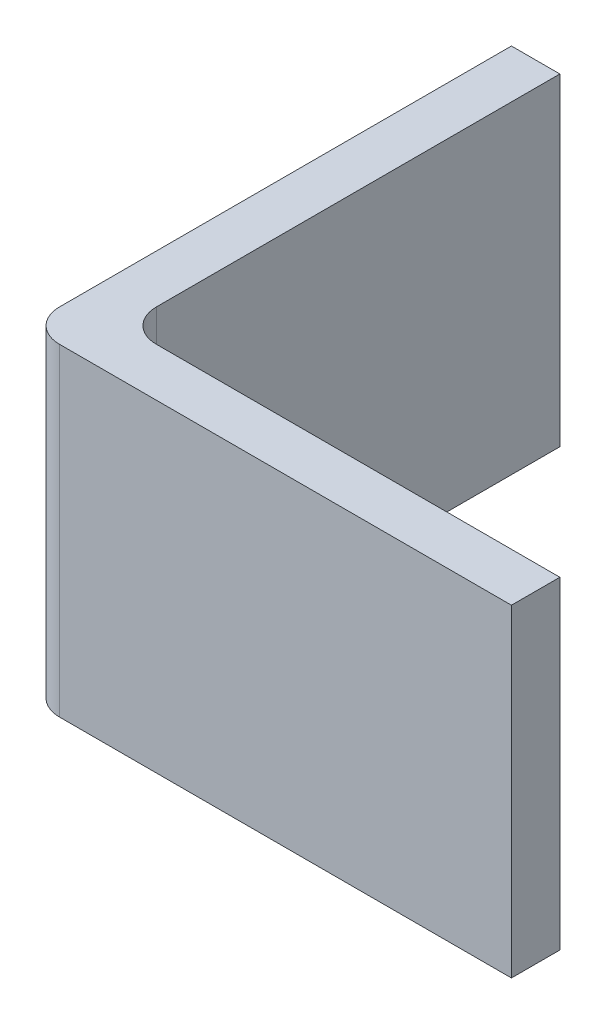
SolidWorks part; units mm, degrees
ref_plane "Спереди" through (0, 0, 0) normal (0, 0, 1) x (1, 0, 0)
ref_plane "Сверху" through (0, 0, 0) normal (0, 1, 0) x (1, 0, 0)
ref_plane "Справа" through (0, 0, 0) normal (1, 0, 0) x (0, 0, -1)
sketch "Эскиз1" plane through (0, 0, 0) normal (0, 1, 0) x (1, 0, 0)
  line L0 (0, 1) -> (0, 15)
  line L5 (0, 15) -> (1.5, 15)
  line L6 (1, 0) -> (15, 0)
  line L7 (15, 0) -> (15, 1.5)
  line L8 (15, 1.5) -> (2.5, 1.5)
  line L9 (1.5, 2.5) -> (1.5, 15)
  arc A0 (1, 0) -> (0, 1) centre (1, 1) cw
  arc A1 (2.5, 1.5) -> (1.5, 2.5) centre (2.5, 2.5) cw
  point P0 (0, 0)
  point P10 (0, 0)
  dimension "D5" = 1
  dimension "D1" = 15
  dimension "D2" = 1.5
  dimension "D3" = 15
  dimension "D4" = 1.5
extrude "Бобышка-Вытянуть1" add sketch "Эскиз1" along normal blind 10
sketch "Эскиз2" plane through (0, 0, 0) normal (0, 0, 1) x (1, 0, 0)
  line L0 (8.25, 0) -> (8.25, 11.3489) construction
  line L3 (1, 0) -> (15, 0) construction
  line L4 (15, 10) -> (15, 0) construction
  point P6 (7.5, 11.3489)
  dimension "D1" = 6.75
